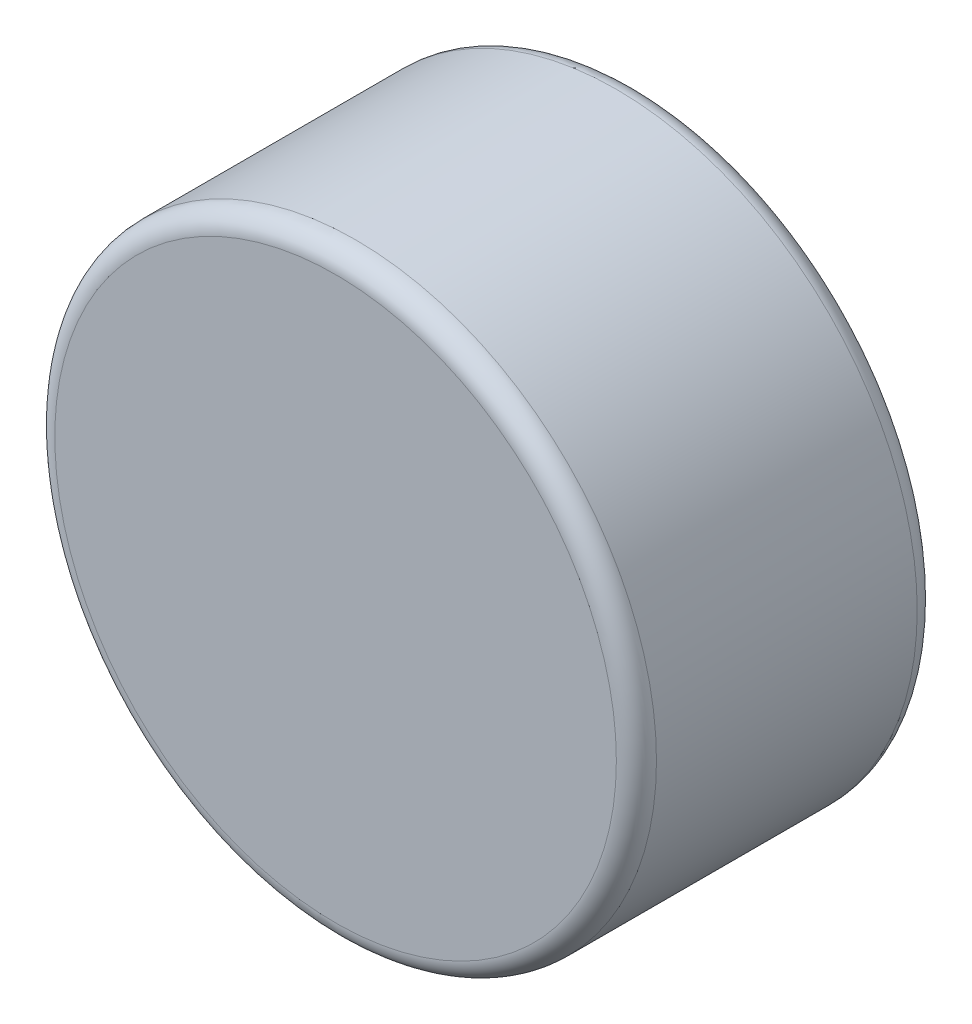
SolidWorks part; units mm, degrees
ref_plane "Piano frontale" through (0, 0, 0) normal (0, 0, 1) x (1, 0, 0)
ref_plane "Piano superiore" through (0, 0, 0) normal (0, 1, 0) x (1, 0, 0)
ref_plane "Piano destro" through (0, 0, 0) normal (1, 0, 0) x (0, 0, -1)
sketch "Schizzo1" plane through (0, 0, 0) normal (0, 0, 1) x (1, 0, 0)
  circle A0 centre (0, 0) radius 3
  dimension "D1" = 6
extrude "Estrusione-Estrusione1" add sketch "Schizzo1" along normal blind 3
fillet "Raccordo1" radius 0.2 2 edges at (3, 0, 0) (3, 0, 3)
equation "\"diametro_magnete\"= 6mm 'diametro magnete"
equation "\"altezza_magnete\"= 3'altezza magnete"
equation "\"D1@Estrusione-Estrusione1\"= \"altezza_magnete\""
equation "\"D1@Schizzo1\"= \"diametro_magnete\""
